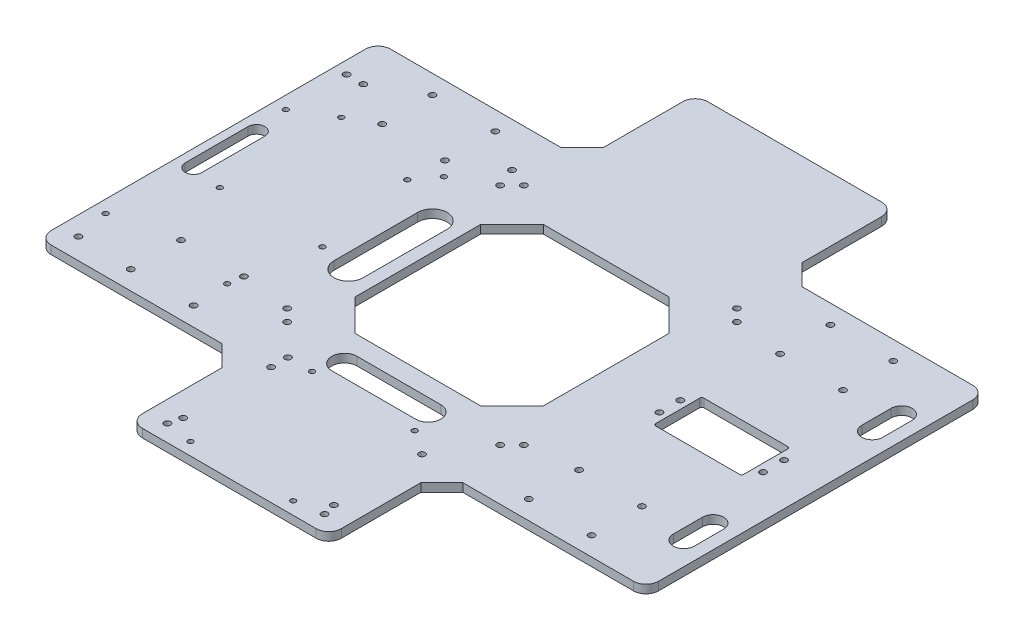
SolidWorks part; units mm, degrees
material "Thornel Mat VMA"
ref_plane "前视基准面" through (0, 0, 0) normal (0, 0, 1) x (1, 0, 0)
ref_plane "上视基准面" through (0, 0, 0) normal (0, 1, 0) x (1, 0, 0)
ref_plane "右视基准面" through (0, 0, 0) normal (1, 0, 0) x (0, 0, -1)
other "Configuration Table"
sketch "草图1" plane through (0, 0, 0) normal (0, 1, 0) x (1, 0, 0)
  line L0 (0, 0) -> (0, 135) construction
  line L1 (-145, -135) -> (145, -135)
  line L2 (-145, -135) -> (-145, 135)
  line L3 (-145, 135) -> (145, 135)
  line L4 (145, -135) -> (145, 135)
  line L5 (-145, -135) -> (145, 135) construction
  line L6 (-145, 135) -> (145, -135) construction
  line L7 (0, 0) -> (145, 0) construction
  line L8 (-47.5, 135) -> (-47.5, 81)
  line L9 (-47.5, 81) -> (-145, 81)
  line L10 (47.5, 81) -> (145, 81)
  line L11 (47.5, 135) -> (47.5, 81)
  line L12 (47.5, -81) -> (145, -81)
  line L13 (47.5, -135) -> (47.5, -81)
  line L14 (-47.5, -81) -> (-145, -81)
  line L15 (-47.5, -135) -> (-47.5, -81)
  point P0 (0, 0)
  dimension "D1" = 290
  dimension "D2" = 270
  dimension "D3" = 162
  dimension "D4" = 95
extrude "凸台-拉伸1" add sketch "草图1" along normal blind 4 contours L15 L1 L13 L12 L4 L10 L11 L3 L8 L9 L2 L14 region at (0, 0, 0)
sketch "草图2" plane through (0, 4, 0) normal (0, 1, 0) x (1, 0, 0)
  line L0 (0, 0) -> (145, 0) construction
  line L1 (145, -81) -> (145, 81) construction
  line L2 (0, 0) -> (0, 135) construction
  line L3 (-47.5, 135) -> (47.5, 135) construction
  line L4 (47.5, 81) -> (145, 81) construction
  circle A0 centre (110, 72) radius 1.5
  circle A1 centre (80, 72) radius 1.5
  circle A2 centre (80, 48) radius 1.5
  circle A3 centre (110, 48) radius 1.5
  circle A4 centre (110, -48) radius 1.5
  circle A5 centre (110, -72) radius 1.5
  circle A6 centre (80, -48) radius 1.5
  circle A7 centre (80, -72) radius 1.5
  circle A8 centre (-80, -72) radius 1.5
  circle A9 centre (-80, -48) radius 1.5
  circle A10 centre (-110, -72) radius 1.5
  circle A11 centre (-110, -48) radius 1.5
  circle A12 centre (-110, 48) radius 1.5
  circle A13 centre (-80, 48) radius 1.5
  circle A14 centre (-80, 72) radius 1.5
  circle A15 centre (-110, 72) radius 1.5
  point P42 (0, 0)
  dimension "D1" = 3
  dimension "D2" = 3
  dimension "D3" = 3
  dimension "D4" = 3
  dimension "D11" = 80
  dimension "D12" = 9
  dimension "D5" = 24
  dimension "D6" = 24
  dimension "D7" = 30
  dimension "D8" = 30
  dimension "D9" = 80
  dimension "D10" = 9
extrude "切除-拉伸1" cut sketch "草图2" against normal blind 4
sketch "草图4" plane through (0, 4, 0) normal (0, 1, 0) x (1, 0, 0)
  line L1 (-45, -45) -> (45, -45)
  line L2 (-45, -45) -> (-45, 45)
  line L3 (-45, 45) -> (45, 45)
  line L4 (45, -45) -> (45, 45)
  line L5 (-45, -45) -> (45, 45) construction
  line L6 (-45, 45) -> (45, -45) construction
  point P0 (0, 0)
  dimension "D1" = 90
  dimension "D2" = 90
extrude "切除-拉伸3" cut sketch "草图4" against normal blind 4
fillet "圆角3" radius 6 8 edges at (-47.5, 2, -135) (47.5, 2, -135) (145, 2, -81) (145, 2, 81) (-47.5, 2, 135) (47.5, 2, 135) (-145, 2, 81) (-145, 2, -81)
chamfer "倒角1" distance 10 angle 45 4 edges at (47.5, 2, 81) (-47.5, 2, 81) (47.5, 2, -81) (-47.5, 2, -81)
sketch "草图7" plane through (0, 4, 0) normal (0, 1, 0) x (1, 0, 0)
  line L0 (0, 0) -> (0, 142.9478) construction
  line L1 (0, 0) -> (-184.5222, 0) construction
  line L2 (-137, -15) -> (-137, 15) construction
  line L5 (-58, -20) -> (-58, 20) construction
  line L6 (-65, -20) -> (-65, 20)
  line L7 (-51, -20) -> (-51, 20)
  line L8 (0, 0) -> (165.4514, 0) construction
  line L14 (-110, 0) -> (-110, 75.2826) construction
  line L15 (134, 38) -> (134, 52) construction
  line L33 (-141, -15) -> (-141, 15)
  line L34 (-133, -15) -> (-133, 15)
  line L35 (63, 0) -> (63, 55.2292) construction
  line L36 (0, -15) -> (172.3256, -15) construction
  line L38 (129, 38) -> (129, 52)
  line L39 (139, 38) -> (139, 52)
  line L40 (134, -38) -> (134, -52) construction
  line L41 (129, -38) -> (129, -52)
  line L42 (139, -38) -> (139, -52)
  arc A2 (-65, -20) -> (-51, -20) centre (-58, -20) ccw
  arc A3 (-51, 20) -> (-65, 20) centre (-58, 20) ccw
  arc A34 (-141, -15) -> (-133, -15) centre (-137, -15) ccw
  arc A35 (-133, 15) -> (-141, 15) centre (-137, 15) ccw
  arc A56 (129, 38) -> (139, 38) centre (134, 38) ccw
  arc A57 (139, 52) -> (129, 52) centre (134, 52) ccw
  arc A58 (129, -38) -> (139, -38) centre (134, -38) cw
  arc A59 (139, -52) -> (129, -52) centre (134, -52) cw
  point P6 (-137, 0)
  point P13 (-58, 0)
  point P21 (134, 45)
  point P37 (134, -45)
  dimension "D2" = 30
  dimension "D5" = 7
  dimension "D8" = 5
  dimension "D10" = 45
  dimension "D9" = 134
  dimension "D3" = 4
  dimension "D23" = 15
  dimension "D1" = 14
  dimension "D4" = 40
  dimension "D6" = 58
  dimension "D7" = 110
  dimension "D20" = 133
  dimension "D24" = 63
extrude "切除-拉伸6" cut sketch "草图7" against normal blind 4
chamfer "倒角2" distance 15 angle 45 4 edges at (45, 2, 45) (-45, 2, 45) (45, 2, -45) (-45, 2, -45)
sketch "草图8" plane through (0, 4, 0) normal (0, 1, 0) x (1, 0, 0)
  line L0 (0, 0) -> (0, 168.9929) construction
  line L1 (0, 0) -> (-169.1558, 0) construction
  line L2 (-103, 0) -> (-103, 65.828) construction
  line L3 (-103, -6) -> (-155.6162, -6) construction
  line L4 (0, 0) -> (-184.1789, 0) construction
  line L5 (0, 0) -> (0, 73.477) construction
  line L6 (-57.5, 81) -> (-139, 81) construction
  circle A15 centre (-139, 60) radius 1.5
  circle A16 centre (-131, 60) radius 1.5
  dimension "D2" = 8
  dimension "D4" = 103
  dimension "D5" = 6
  dimension "D6" = 0
  dimension "D7" = 3
  dimension "D8" = 3
  dimension "D11" = 28
  dimension "D12" = 36
  dimension "D10" = 21
extrude "切除-拉伸7" cut sketch "草图8" against normal blind 4
sketch "草图9" plane through (0, 4, 0) normal (0, 1, 0) x (1, 0, 0)
  line L0 (0, 0) -> (0, 165.3902) construction
  line L1 (0, 0) -> (179.4814, 0) construction
  line L2 (50.8431, 56.5) -> (56.5, 50.8431) construction
  line L3 (-62.5, -62.5) -> (62.5, -62.5) construction
  line L4 (-62.5, -62.5) -> (-62.5, 62.5) construction
  line L5 (-62.5, 62.5) -> (62.5, 62.5) construction
  line L6 (62.5, -62.5) -> (62.5, 62.5) construction
  line L7 (-62.5, -62.5) -> (62.5, 62.5) construction
  line L8 (-62.5, 62.5) -> (62.5, -62.5) construction
  line L18 (-50.3018, -50.3018) -> (40.4104, 40.4104) construction
  line L23 (-50.8431, -50.8431) -> (45.8431, 45.8431) construction
  line L24 (-48.3431, 48.3431) -> (48.3431, -48.3431) construction
  line L29 (-52.5221, -52.5221) -> (52.5221, 52.5221) construction
  line L30 (-52.5221, 52.5221) -> (52.5221, -52.5221) construction
  circle A0 centre (50.8431, 56.5) radius 1.5
  circle A1 centre (56.5, 50.8431) radius 1.5
  circle A2 centre (56.5, -50.8431) radius 1.5
  circle A3 centre (50.8431, -56.5) radius 1.5
  circle A4 centre (-50.8431, -56.5) radius 1.5
  circle A5 centre (-56.5, -50.8431) radius 1.5
  circle A6 centre (-56.5, 50.8431) radius 1.5
  circle A7 centre (-50.8431, 56.5) radius 1.5
  circle A8 centre (-37.5, -127) radius 1.5
  circle A9 centre (37.5, -127) radius 1.5
  dimension "D3" = 3
  dimension "D4" = 3
  dimension "D6" = 8
  dimension "D9" = 3
  dimension "D11" = 127
  dimension "D1" = 125
  dimension "D2" = 125
  dimension "D5" = 45
  dimension "D7" = 6
  dimension "D8" = 6
  dimension "D10" = 37.5
extrude "切除-拉伸8" cut sketch "草图9" against normal blind 4
sketch "草图10" plane through (0, 4, 0) normal (0, 1, 0) x (1, 0, 0)
  line L0 (0, 0) -> (173.0266, 0) construction
  line L1 (0, 0) -> (0, 114.2255) construction
sketch "草图11" plane through (0, 4, 0) normal (0, 1, 0) x (1, 0, 0)
  line L0 (0, 0) -> (183.5565, 0) construction
  line L1 (0, 0) -> (0, -155.5612) construction
sketch "草图12" plane through (0, 4, 0) normal (0, 1, 0) x (1, 0, 0)
  line L0 (-20, -60) -> (20, -60) construction
  line L1 (0, 0) -> (0, -155.5612) construction
  line L2 (-20, -54) -> (20, -54)
  line L3 (-20, -66) -> (20, -66)
  line L4 (0, 0) -> (173.0266, 0) construction
  arc A0 (-20, -54) -> (-20, -66) centre (-20, -60) ccw
  arc A1 (20, -66) -> (20, -54) centre (20, -60) ccw
  point P4 (0, -60)
  dimension "D2" = 6
  dimension "D1" = 40
  dimension "D3" = 60
extrude "切除-拉伸9" cut sketch "草图12" against normal blind 10
sketch "草图14" plane through (0, 4, 0) normal (0, 1, 0) x (1, 0, 0)
  line L0 (0, 0) -> (0, -145.4864) construction
  line L1 (0, 0) -> (173.1076, 0) construction
  line L2 (0, -100) -> (89.1596, -100) construction
  circle A0 centre (36, -79) radius 1.5
  circle A1 centre (36, -121) radius 1.5
  circle A2 centre (-36, -121) radius 1.5
  circle A3 centre (-36, -79) radius 1.5
  circle A4 centre (-24.5, -71) radius 1.25
  circle A5 centre (24.5, -71) radius 1.25
  circle A6 centre (24.5, -129) radius 1.25
  circle A7 centre (-24.5, -129) radius 1.25
  dimension "D1" = 3
  dimension "D2" = 42
  dimension "D3" = 72
  dimension "D5" = 2.5
  dimension "D6" = 49
  dimension "D7" = 58
  dimension "D4" = 100
extrude "切除-拉伸10" cut sketch "草图14" against normal blind 10
sketch "草图15" plane through (0, 4, 0) normal (0, 1, 0) x (1, 0, 0)
  line L0 (0, 0) -> (175.5609, 0) construction
  line L1 (0, 0) -> (0, 158.0719) construction
  line L2 (100.11, 0) -> (100.11, 39.6302) construction
  line L3 (79.11, -11.5) -> (121.11, -11.5)
  line L4 (79.11, -11.5) -> (79.11, 11.5)
  line L5 (79.11, 11.5) -> (121.11, 11.5)
  line L6 (121.11, -11.5) -> (121.11, 11.5)
  line L7 (79.11, -11.5) -> (121.11, 11.5) construction
  line L8 (79.11, 11.5) -> (121.11, -11.5) construction
  line L9 (110, 0) -> (110, 79.3701) construction
  circle A0 centre (75.36, 5) radius 1.5
  circle A2 centre (75.36, -5) radius 1.5
  circle A4 centre (124.86, -5) radius 1.5
  circle A5 centre (124.86, 5) radius 1.5
  point P3 (100.11, 0)
  dimension "D3" = 10
  dimension "D4" = 3
  dimension "D5" = 49.5
  dimension "D1" = 42
  dimension "D2" = 23
  dimension "D6" = 9.89
  dimension "D7" = 110
extrude "切除-拉伸11" cut sketch "草图15" against normal blind 10
fillet "圆角4" radius 1 4 edges at (79.11, 2, 11.5) (121.11, 2, 11.5) (121.11, 2, -11.5) (79.11, 2, -11.5)
sketch "草图16" plane through (0, 4, 0) normal (0, 1, 0) x (1, 0, 0)
  line L0 (0, 12) -> (-202.0071, 12) construction
  line L1 (0, 12) -> (0, 203.0309) construction
  line L2 (-98, -2.3134) -> (-98, 98.9217) construction
  line L4 (0, 0) -> (0, 12) construction
  line L5 (0, 0) -> (-183.682, 0) construction
  circle A0 centre (-73.5, 41) radius 1.25
  circle A1 centre (-122.5, 41) radius 1.25
  circle A2 centre (-73.5, -17) radius 1.25
  circle A3 centre (-122.5, -17) radius 1.25
  dimension "D1" = 58
  dimension "D2" = 49
  dimension "D3" = 2.5
  dimension "D4" = 98
  dimension "D5" = 12
extrude "切除-拉伸12" cut sketch "草图16" against normal blind 10
sketch "草图19" plane through (0, 4, 0) normal (0, 1, 0) x (1, 0, 0)
  line L0 (0, 0) -> (-178.7427, 0) construction
  line L1 (0, 0) -> (0, 171.7177) construction
  line L2 (-98, -10.9053) -> (-98, 46.7773) construction
  line L3 (-98, -7.4) -> (-15.7423, -7.4) construction
  circle A0 centre (-65, 50) radius 1.5
  circle A1 centre (-131, 50) radius 1.5
  circle A2 centre (-65, -64.8) radius 1.5
  circle A3 centre (-131, -64.8) radius 1.5
  dimension "D1" = 3
  dimension "D2" = 114.8
  dimension "D3" = 66
  dimension "D4" = 98
  dimension "D5" = 7.4
sketch "草图20" plane through (0, 4, 0) normal (0, 1, 0) x (1, 0, 0)
  line L0 (0, 0) -> (0, 140.7476) construction
  line L1 (0, 0) -> (-188.6657, 0) construction
  circle A0 centre (-60, 60) radius 1.5
  dimension "D1" = 3
  dimension "D2" = 60
  dimension "D3" = 60
sketch "草图22" plane through (0, 4, 0) normal (0, 1, 0) x (1, 0, 0)
  line L0 (0, 0) -> (154.1719, 0) construction
  line L1 (61, 0) -> (61, 40.4074) construction
  circle A0 centre (73, 13) radius 1.5
  circle A1 centre (49, 13) radius 1.5
  circle A2 centre (73, -13) radius 1.5
  circle A3 centre (49, -13) radius 1.5
  dimension "D1" = 24
  dimension "D2" = 26
  dimension "D3" = 3
  dimension "D4" = 61
sketch "草图23" plane through (0, 4, 0) normal (0, 1, 0) x (1, 0, 0)
  line L0 (0, 0) -> (-194.1261, 0) construction
  line L1 (-110, 0) -> (-110, 133.2192) construction
  line L3 (0, 0) -> (0, 84.0673) construction
  line L4 (0, -12) -> (-198.9065, -12) construction
  circle A0 centre (-81, 31) radius 1.25
  circle A3 centre (-139, 31) radius 1.25
  circle A4 centre (-81, -55) radius 1.25
  circle A5 centre (-139, -55) radius 1.25
  dimension "D1" = 2.5
  dimension "D2" = 58
  dimension "D3" = 86
  dimension "D5" = 12
  dimension "D4" = 110
extrude "切除-拉伸14" cut sketch "草图23" against normal blind 10
sketch "草图24" plane through (0, 4, 0) normal (0, 1, 0) x (1, 0, 0)
  line L0 (0, 0) -> (-236.5327, 0) construction
  line L1 (0, 0) -> (0, -171.9197) construction
  line L2 (0, -96) -> (-165.3693, -96) construction
  line L3 (-86, 0) -> (-86, -158.0192) construction
  circle A0 centre (-136, -71) radius 1.5
  circle A1 centre (-36, -71) radius 1.5
  circle A2 centre (-36, -121) radius 1.5
  dimension "D1" = 3
  dimension "D2" = 100
  dimension "D3" = 50
  dimension "D4" = 96
  dimension "D5" = 86
extrude "切除-拉伸15" cut sketch "草图24" against normal blind 10
extrude "切除-拉伸16" cut sketch "草图20" against normal blind 10
sketch "草图25" plane through (0, 4, 0) normal (0, 1, 0) x (1, 0, 0)
  line L0 (0, 0) -> (201.6978, 0) construction
  line L1 (0, 0) -> (0, 184.1709) construction
sketch "草图26" plane through (0, 0, 0) normal (1, 0, 0) x (0, 0, -1)
  line L0 (0, 0) -> (0, 117.1786) construction
